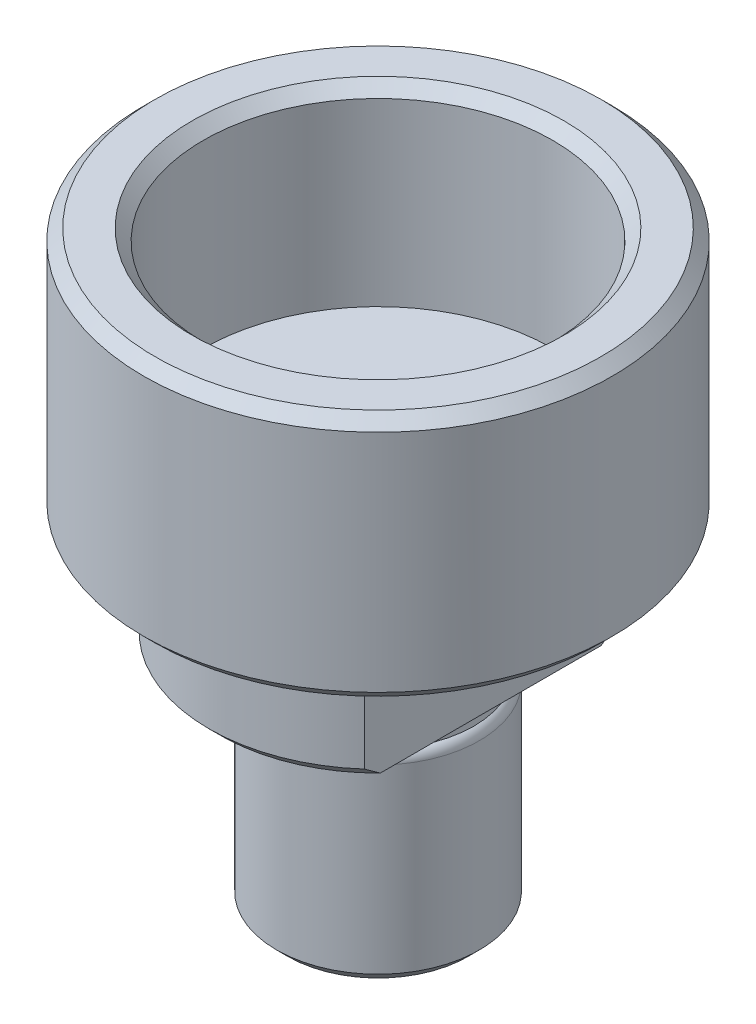
SolidWorks part; units mm, degrees
ref_plane "Alzado" through (0, 0, 0) normal (0, 0, 1) x (1, 0, 0)
ref_plane "Planta" through (0, 0, 0) normal (0, 1, 0) x (1, 0, 0)
ref_plane "Vista lateral" through (0, 0, 0) normal (1, 0, 0) x (0, 0, -1)
sketch "Croquis1" plane through (0, 0, 0) normal (0, 0, 1) x (1, 0, 0)
  line L0 (0, 50.375) -> (0, -55.9379) construction
  line L1 (15.5, 52) -> (20.7902, 52)
  line L2 (20.7902, 52) -> (20.7902, 30)
  line L3 (20.7902, 30) -> (15, 30)
  line L4 (15, 30) -> (15, 20)
  line L5 (15, 20) -> (8.5, 20)
  line L6 (9, 17.9517) -> (9, 0)
  line L7 (9, 0) -> (4.7625, 0)
  line L8 (4.7625, 0) -> (4.7625, 30)
  line L9 (4.2625, 34) -> (5.2625, 35)
  line L10 (15.5, 35) -> (15.5, 52)
  line L12 (8.5, 20) -> (8.5, 17.9517)
  line L13 (8.5, 17.9517) -> (9, 17.9517)
  line L14 (4.7625, 30) -> (4.2625, 30)
  line L15 (4.2625, 30) -> (4.2625, 34)
  line L16 (5.2625, 35) -> (15.5, 35)
  point P19 (4.2625, 35)
  dimension "D1" = 22
  dimension "D2" = 10
  dimension "D3" = 30
  dimension "D4" = 4.7625
  dimension "D5" = 9
  dimension "D6" = 15.5
  dimension "D7" = 17
  dimension "D8" = 5
  dimension "D9" = 0.5
  dimension "D10" = 15
  dimension "D12" = 8.5
revolve "Revolución1" add sketch "Croquis1" angle 360 about L0
chamfer "Chaflán1" distance 1 angle 45 1 edges at (0, 0, 9)
fillet "Redondeo1" radius 1 1 edges at (0, 17.9517, 9)
chamfer "Chaflán2" distance 1 angle 45 4 edges at (0, 52, 15.5) (0, 52, 20.7902) (0, 30, 20.7902) (0, 20, 15)
sketch "Croquis3" plane through (0, 0, 0) normal (0, -1, 0) x (1, 0, 0)
  line L0 (0, 18.5909) -> (0, -22.1588) construction
  line L1 (10, 11.1803) -> (10, -11.1803)
  line L2 (-10, 11.1803) -> (-10, -11.1803)
  line L3 (10, 11.1803) -> (24.8279, 11.1803)
  line L4 (24.8279, 11.1803) -> (24.246, -11.1803)
  line L5 (24.246, -11.1803) -> (10, -11.1803)
  line L6 (-10, 11.1803) -> (-24.7309, 11.1803)
  line L7 (-24.7309, 11.1803) -> (-24.7309, -11.1803)
  line L8 (-24.7309, -11.1803) -> (-10, -11.1803)
  circle A0 centre (0, 0) radius 15 construction
  circle A1 centre (0, 0) radius 15 construction
  dimension "D1" = 10
  dimension "D2" = 10
extrude "Cortar-Extruir1" cut sketch "Croquis3" against normal up to surface (30 mm away) up to face at (0, 30, 19.7902)
